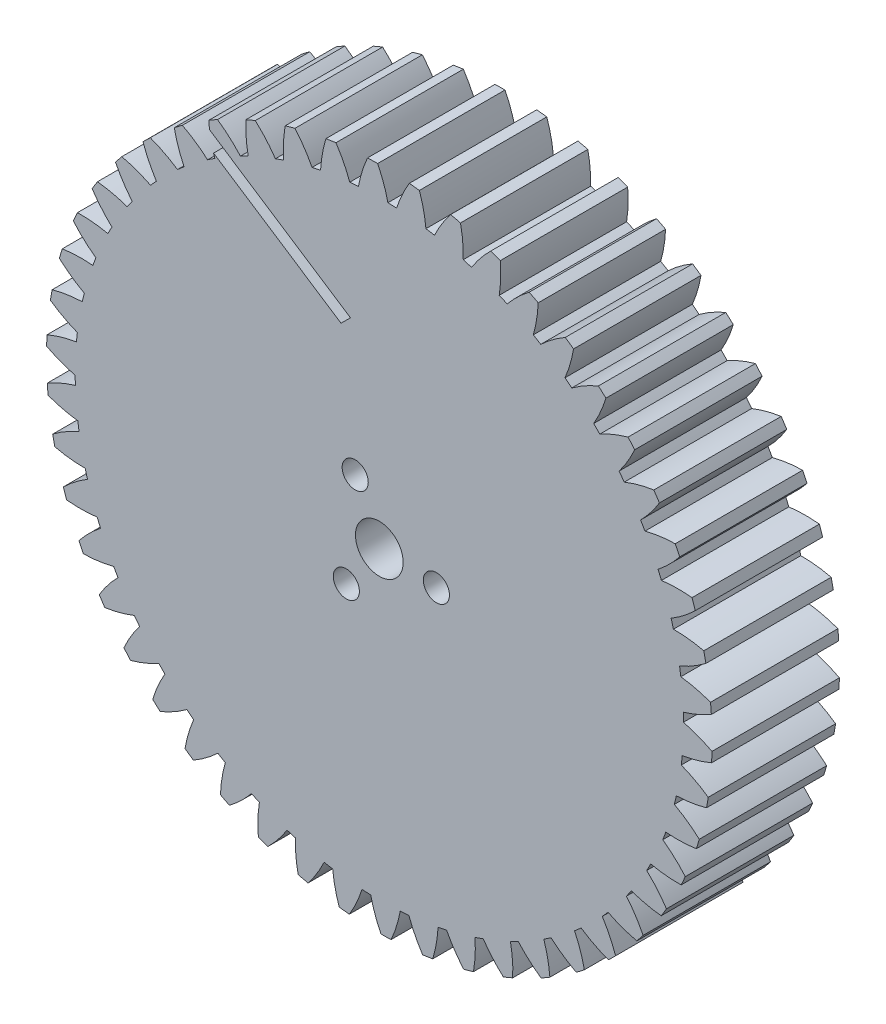
SolidWorks part; units mm, degrees
ref_plane "Front Plane" through (0, 0, 0) normal (0, 0, 1) x (1, 0, 0)
ref_plane "Top Plane" through (0, 0, 0) normal (0, 1, 0) x (1, 0, 0)
ref_plane "Right Plane" through (0, 0, 0) normal (1, 0, 0) x (0, 0, -1)
sketch "Sketch1" plane through (0, 0, 0) normal (0, 0, 1) x (1, 0, 0)
  circle A0 centre (0, 0) radius 52.3715
extrude "Boss-Extrude1" add sketch "Sketch1" along normal blind 10
extrude "Cut-Extrude1" cut sketch "Sketch2" against normal through all
sketch "Sketch2" plane through (-27.9652, -165.9867, 67.9694) normal (0, 0, 1) x (1, 0, 0)
  circle A200 centre (27.9652, 165.9867) radius 130.5991
  arc A600 (44.796, 182.9215) -> (45.7553, 185.1213) centre (36.0583, 188.041) ccw
  arc A601 (45.7553, 185.1213) -> (45.1635, 185.6549) centre (27.9652, 165.9867) ccw
  arc A602 (45.1635, 185.6549) -> (43.0744, 184.4739) centre (49.0675, 176.3106) ccw
  arc A603 (43.0744, 184.4739) -> (42.5408, 184.8975) centre (27.9652, 165.9867) ccw
  arc A604 (42.5408, 184.8975) -> (43.2168, 187.2001) centre (33.2304, 188.8814) ccw
  arc A605 (43.2168, 187.2001) -> (42.5628, 187.6553) centre (27.9652, 165.9867) ccw
  arc A606 (42.5628, 187.6553) -> (40.6382, 186.2218) centre (47.6071, 178.874) ccw
  arc A607 (40.6382, 186.2218) -> (40.0557, 186.5751) centre (27.9652, 165.9867) ccw
  arc A608 (40.0557, 186.5751) -> (40.4378, 188.9444) centre (30.3194, 189.3608) ccw
  arc A609 (40.4378, 188.9444) -> (39.7319, 189.314) centre (27.9652, 165.9867) ccw
  arc A610 (39.7319, 189.314) -> (38.0021, 187.6506) centre (45.8371, 181.2342) ccw
  arc A611 (38.0021, 187.6506) -> (37.38, 187.9281) centre (27.9652, 165.9867) ccw
  arc A612 (37.38, 187.9281) -> (37.4621, 190.3266) centre (27.3713, 189.4715) ccw
  arc A613 (37.4621, 190.3266) -> (36.7155, 190.6049) centre (27.9652, 165.9867) ccw
  arc A614 (36.7155, 190.6049) -> (35.2078, 188.7377) centre (43.7851, 183.3539) ccw
  arc A615 (35.2078, 188.7377) -> (34.5557, 188.9351) centre (27.9652, 165.9867) ccw
  arc A616 (34.5557, 188.9351) -> (34.3366, 191.3249) centre (24.4325, 189.2119) ccw
  arc A617 (34.3366, 191.3249) -> (33.561, 191.5074) centre (27.9652, 165.9867) ccw
  arc A618 (33.561, 191.5074) -> (32.2992, 189.4661) centre (41.4837, 185.1997) ccw
  arc A619 (32.2992, 189.4661) -> (31.6276, 189.5802) centre (27.9652, 165.9867) ccw
  arc A620 (31.6276, 189.5802) -> (31.1107, 191.9237) centre (21.5495, 188.586) ccw
  arc A621 (31.1107, 191.9237) -> (30.3183, 192.0075) centre (27.9652, 165.9867) ccw
  arc A622 (30.3183, 192.0075) -> (29.3223, 189.8241) centre (38.9691, 186.7425) ccw
  arc A623 (29.3223, 189.8241) -> (28.6416, 189.8531) centre (27.9652, 165.9867) ccw
  arc A624 (28.6416, 189.8531) -> (27.8351, 192.1134) centre (18.7676, 187.6037) ccw
  arc A625 (27.8351, 192.1134) -> (27.0384, 192.0973) centre (27.9652, 165.9867) ccw
  arc A626 (27.0384, 192.0973) -> (26.324, 189.8062) centre (36.2809, 187.958) ccw
  arc A627 (26.324, 189.8062) -> (25.6451, 189.7497) centre (27.9652, 165.9867) ccw
  arc A628 (25.6451, 189.7497) -> (24.5616, 191.8911) centre (16.1308, 186.2805) ccw
  arc A629 (24.5616, 191.8911) -> (23.7732, 191.7752) centre (27.9652, 165.9867) ccw
  arc A630 (23.7732, 191.7752) -> (23.3515, 189.4127) centre (33.4616, 188.827) ccw
  arc A631 (23.3515, 189.4127) -> (22.6851, 189.2715) centre (27.9652, 165.9867) ccw
  arc A632 (22.6851, 189.2715) -> (21.3417, 191.2602) centre (13.6807, 184.6372) ccw
  arc A633 (21.3417, 191.2602) -> (20.5741, 191.0465) centre (27.9652, 165.9867) ccw
  arc A634 (20.5741, 191.0465) -> (20.4519, 188.6497) centre (30.5556, 189.3358) ccw
  arc A635 (20.4519, 188.6497) -> (19.8083, 188.4262) centre (27.9652, 165.9867) ccw
  arc A636 (19.8083, 188.4262) -> (18.2264, 190.2308) centre (11.4558, 182.6998) ccw
  arc A637 (18.2264, 190.2308) -> (17.4916, 189.9225) centre (27.9652, 165.9867) ccw
  arc A638 (17.4916, 189.9225) -> (17.6707, 187.5294) centre (27.6088, 189.4763) ccw
  arc A639 (17.6707, 187.5294) -> (17.0602, 187.2269) centre (27.9652, 165.9867) ccw
  arc A640 (17.0602, 187.2269) -> (15.2646, 188.819) centre (9.4913, 180.4988) ccw
  arc A641 (15.2646, 188.819) -> (14.5742, 188.4211) centre (27.9652, 165.9867) ccw
  arc A642 (14.5742, 188.4211) -> (15.0518, 186.0692) centre (24.6675, 189.2464) ccw
  arc A643 (15.0518, 186.0692) -> (14.4841, 185.6926) centre (27.9652, 165.9867) ccw
  arc A644 (14.4841, 185.6926) -> (12.5031, 187.0472) centre (7.8181, 178.069) ccw
  arc A645 (12.5031, 187.0472) -> (11.868, 186.5659) centre (27.9652, 165.9867) ccw
  arc A646 (11.868, 186.5659) -> (12.6367, 184.2924) centre (21.7783, 188.6497) ccw
  arc A647 (12.6367, 184.2924) -> (12.1206, 183.8476) centre (27.9652, 165.9867) ccw
  arc A648 (12.1206, 183.8476) -> (9.9854, 184.9432) centre (6.4626, 175.4486) ccw
  arc A649 (9.9854, 184.9432) -> (9.4157, 184.3861) centre (27.9652, 165.9867) ccw
  arc A650 (9.4157, 184.3861) -> (10.4632, 182.2269) centre (18.9867, 187.6956) ccw
  arc A651 (10.4632, 182.2269) -> (10.007, 181.7209) centre (27.9652, 165.9867) ccw
  arc A652 (10.007, 181.7209) -> (7.7513, 182.5402) centre (5.4463, 172.679) ccw
  arc A653 (7.7513, 182.5402) -> (7.2559, 181.9161) centre (27.9652, 165.9867) ccw
  arc A654 (7.2559, 181.9161) -> (8.5658, 179.9053) centre (16.3366, 186.3991) ccw
  arc A655 (8.5658, 179.9053) -> (8.1766, 179.3461) centre (27.9652, 165.9867) ccw
  arc A656 (8.1766, 179.3461) -> (5.836, 179.8762) centre (4.7851, 169.8039) ccw
  arc A657 (5.836, 179.8762) -> (5.4228, 179.195) centre (27.9652, 165.9867) ccw
  arc A658 (5.4228, 179.195) -> (6.9743, 177.3641) centre (13.87, 184.7807) ccw
  arc A659 (6.9743, 177.3641) -> (6.6582, 176.7606) centre (27.9652, 165.9867) ccw
  arc A660 (6.6582, 176.7606) -> (4.2697, 176.9932) centre (4.4895, 166.8686) ccw
  arc A661 (4.2697, 176.9932) -> (3.9451, 176.2655) centre (27.9652, 165.9867) ccw
  arc A662 (3.9451, 176.2655) -> (5.7139, 174.6435) centre (11.6256, 182.8659) ccw
  arc A663 (5.7139, 174.6435) -> (5.4759, 174.0052) centre (27.9652, 165.9867) ccw
  arc A664 (5.4759, 174.0052) -> (3.0771, 173.9365) centre (4.564, 163.9193) ccw
  arc A665 (3.0771, 173.9365) -> (2.8462, 173.1739) centre (27.9652, 165.9867) ccw
  arc A666 (2.8462, 173.1739) -> (4.8043, 171.7864) centre (9.6389, 180.6849) ccw
  arc A667 (4.8043, 171.7864) -> (4.6483, 171.1233) centre (27.9652, 165.9867) ccw
  arc A668 (4.6483, 171.1233) -> (2.2769, 170.7545) centre (5.0077, 161.0027) ccw
  arc A669 (2.2769, 170.7545) -> (2.1435, 169.969) centre (27.9652, 165.9867) ccw
  arc A670 (2.1435, 169.969) -> (4.2601, 168.8379) centre (7.9413, 178.2721) ccw
  arc A671 (4.2601, 168.8379) -> (4.1884, 168.1604) centre (27.9652, 165.9867) ccw
  arc A672 (4.1884, 168.1604) -> (1.8819, 167.4974) centre (5.8134, 158.1646) ccw
  arc A673 (1.8819, 167.4974) -> (1.848, 166.7013) centre (27.9652, 165.9867) ccw
  arc A674 (1.848, 166.7013) -> (4.0896, 165.8444) centre (6.5594, 175.6656) ccw
  arc A675 (4.0896, 165.8444) -> (4.1034, 165.1632) centre (27.9652, 165.9867) ccw
  arc A676 (4.1034, 165.1632) -> (1.8983, 164.2163) centre (6.9684, 155.4499) ccw
  arc A677 (1.8983, 164.2163) -> (1.9644, 163.4223) centre (27.9652, 165.9867) ccw
  arc A678 (1.9644, 163.4223) -> (4.2957, 162.8531) centre (5.5151, 172.9064) ccw
  arc A679 (4.2957, 162.8531) -> (4.3948, 162.179) centre (27.9652, 165.9867) ccw
  arc A680 (4.3948, 162.179) -> (2.3257, 160.9632) centre (8.4546, 152.9014) ccw
  arc A681 (2.3257, 160.9632) -> (2.4908, 160.1837) centre (27.9652, 165.9867) ccw
  arc A682 (2.4908, 160.1837) -> (4.8751, 159.9112) centre (4.8249, 170.0381) ccw
  arc A683 (4.8751, 159.9112) -> (5.0579, 159.2549) centre (27.9652, 165.9867) ccw
  arc A684 (5.0579, 159.2549) -> (3.1575, 157.7894) centre (10.2485, 150.5593) ccw
  arc A685 (3.1575, 157.7894) -> (3.419, 157.0367) centre (27.9652, 165.9867) ccw
  arc A686 (3.419, 157.0367) -> (5.8187, 157.0652) centre (4.4996, 167.1059) ccw
  arc A687 (5.8187, 157.0652) -> (6.0822, 156.4369) centre (27.9652, 165.9867) ccw
  arc A688 (6.0822, 156.4369) -> (4.3805, 154.7448) centre (12.3217, 148.4604) ccw
  arc A689 (4.3805, 154.7448) -> (4.7343, 154.0308) centre (27.9652, 165.9867) ccw
  arc A690 (4.7343, 154.0308) -> (7.1115, 154.3598) centre (4.5443, 164.156) ccw
  arc A691 (7.1115, 154.3598) -> (7.4517, 153.7696) centre (27.9652, 165.9867) ccw
  arc A692 (7.4517, 153.7696) -> (5.9755, 151.8775) centre (14.6417, 146.638) ccw
  arc A693 (5.9755, 151.8775) -> (6.4159, 151.2135) centre (27.9652, 165.9867) ccw
  arc A694 (6.4159, 151.2135) -> (8.7331, 151.8378) centre (4.9585, 161.2351) ccw
  arc A695 (8.7331, 151.8378) -> (9.1446, 151.2949) centre (27.9652, 165.9867) ccw
  arc A696 (9.1446, 151.2949) -> (7.9172, 149.2327) centre (17.1718, 145.1207) ccw
  arc A697 (7.9172, 149.2327) -> (8.4374, 148.6291) centre (27.9652, 165.9867) ccw
  arc A698 (8.4374, 148.6291) -> (10.6581, 149.539) centre (5.7354, 158.389) ccw
  arc A699 (10.6581, 149.539) -> (11.1344, 149.0519) centre (27.9652, 165.9867) ccw
  arc A700 (11.1344, 149.0519) -> (10.1751, 146.8521) centre (19.8721, 143.9324) ccw
  arc A701 (10.1751, 146.8521) -> (10.7669, 146.3185) centre (27.9652, 165.9867) ccw
  arc A702 (10.7669, 146.3185) -> (12.856, 147.4995) centre (6.8629, 155.6628) ccw
  arc A703 (12.856, 147.4995) -> (13.3896, 147.076) centre (27.9652, 165.9867) ccw
  arc A704 (13.3896, 147.076) -> (12.7136, 144.7733) centre (22.7001, 143.092) ccw
  arc A705 (12.7136, 144.7733) -> (13.3676, 144.3181) centre (27.9652, 165.9867) ccw
  arc A706 (13.3676, 144.3181) -> (15.2922, 145.7516) centre (8.3233, 153.0994) ccw
  arc A707 (15.2922, 145.7516) -> (15.8747, 145.3983) centre (27.9652, 165.9867) ccw
  arc A708 (15.8747, 145.3983) -> (15.4926, 143.029) centre (25.6111, 142.6127) ccw
  arc A709 (15.4926, 143.029) -> (16.1985, 142.6594) centre (27.9652, 165.9867) ccw
  arc A710 (16.1985, 142.6594) -> (17.9283, 144.3228) centre (10.0934, 150.7392) ccw
  arc A711 (17.9283, 144.3228) -> (18.5505, 144.0453) centre (27.9652, 165.9867) ccw
  arc A712 (18.5505, 144.0453) -> (18.4683, 141.6468) centre (28.5592, 142.5019) ccw
  arc A713 (18.4683, 141.6468) -> (19.215, 141.3686) centre (27.9652, 165.9867) ccw
  arc A714 (19.215, 141.3686) -> (20.7226, 143.2357) centre (12.1453, 148.6195) ccw
  arc A715 (20.7226, 143.2357) -> (21.3747, 143.0383) centre (27.9652, 165.9867) ccw
  arc A716 (21.3747, 143.0383) -> (21.5938, 140.6485) centre (31.4979, 142.7615) ccw
  arc A717 (21.5938, 140.6485) -> (22.3694, 140.466) centre (27.9652, 165.9867) ccw
  arc A718 (22.3694, 140.466) -> (23.6312, 142.5074) centre (14.4467, 146.7737) ccw
  arc A719 (23.6312, 142.5074) -> (24.3029, 142.3933) centre (27.9652, 165.9867) ccw
  arc A720 (24.3029, 142.3933) -> (24.8198, 140.0497) centre (34.3809, 143.3874) ccw
  arc A721 (24.8198, 140.0497) -> (25.6121, 139.9659) centre (27.9652, 165.9867) ccw
  arc A722 (25.6121, 139.9659) -> (26.6081, 142.1493) centre (16.9614, 145.2309) ccw
  arc A723 (26.6081, 142.1493) -> (27.2888, 142.1203) centre (27.9652, 165.9867) ccw
  arc A724 (27.2888, 142.1203) -> (28.0953, 139.86) centre (37.1628, 144.3697) ccw
  arc A725 (28.0953, 139.86) -> (28.892, 139.8762) centre (27.9652, 165.9867) ccw
  arc A726 (28.892, 139.8762) -> (29.6065, 142.1672) centre (19.6495, 144.0154) ccw
  arc A727 (29.6065, 142.1672) -> (30.2854, 142.2237) centre (27.9652, 165.9867) ccw
  arc A728 (30.2854, 142.2237) -> (31.3689, 140.0824) centre (39.7996, 145.693) ccw
  arc A729 (31.3689, 140.0824) -> (32.1572, 140.1982) centre (27.9652, 165.9867) ccw
  arc A730 (32.1572, 140.1982) -> (32.5789, 142.5607) centre (22.4688, 143.1464) ccw
  arc A731 (32.5789, 142.5607) -> (33.2454, 142.7019) centre (27.9652, 165.9867) ccw
  arc A732 (33.2454, 142.7019) -> (34.5887, 140.7132) centre (42.2498, 147.3362) ccw
  arc A733 (34.5887, 140.7132) -> (35.3563, 140.9269) centre (27.9652, 165.9867) ccw
  arc A734 (35.3563, 140.9269) -> (35.4786, 143.3237) centre (25.3748, 142.6377) ccw
  arc A735 (35.4786, 143.3237) -> (36.1221, 143.5473) centre (27.9652, 165.9867) ccw
  arc A736 (36.1221, 143.5473) -> (37.7041, 141.7426) centre (44.4746, 149.2736) ccw
  arc A737 (37.7041, 141.7426) -> (38.4388, 142.0509) centre (27.9652, 165.9867) ccw
  arc A738 (38.4388, 142.0509) -> (38.2598, 144.4441) centre (28.3217, 142.4971) ccw
  arc A739 (38.2598, 144.4441) -> (38.8702, 144.7465) centre (27.9652, 165.9867) ccw
  arc A740 (38.8702, 144.7465) -> (40.6659, 143.1544) centre (46.4392, 151.4746) ccw
  arc A741 (40.6659, 143.1544) -> (41.3562, 143.5523) centre (27.9652, 165.9867) ccw
  arc A742 (41.3562, 143.5523) -> (40.8786, 145.9042) centre (31.2629, 142.727) ccw
  arc A743 (40.8786, 145.9042) -> (41.4463, 146.2808) centre (27.9652, 165.9867) ccw
  arc A744 (41.4463, 146.2808) -> (43.4274, 144.9263) centre (48.1123, 153.9044) ccw
  arc A745 (43.4274, 144.9263) -> (44.0624, 145.4076) centre (27.9652, 165.9867) ccw
  arc A746 (44.0624, 145.4076) -> (43.2938, 147.681) centre (34.1521, 143.3237) ccw
  arc A747 (43.2938, 147.681) -> (43.8098, 148.1258) centre (27.9652, 165.9867) ccw
  arc A748 (43.8098, 148.1258) -> (45.945, 147.0303) centre (49.4678, 156.5248) ccw
  arc A749 (45.945, 147.0303) -> (46.5147, 147.5874) centre (27.9652, 165.9867) ccw
  arc A750 (46.5147, 147.5874) -> (45.4672, 149.7465) centre (36.9437, 144.2778) ccw
  arc A751 (45.4672, 149.7465) -> (45.9234, 150.2525) centre (27.9652, 165.9867) ccw
  arc A752 (45.9234, 150.2525) -> (48.1791, 149.4332) centre (50.4841, 159.2944) ccw
  arc A753 (48.1791, 149.4332) -> (48.6745, 150.0573) centre (27.9652, 165.9867) ccw
  arc A754 (48.6745, 150.0573) -> (47.3646, 152.0682) centre (39.5938, 145.5743) ccw
  arc A755 (47.3646, 152.0682) -> (47.7538, 152.6273) centre (27.9652, 165.9867) ccw
  arc A756 (47.7538, 152.6273) -> (50.0944, 152.0972) centre (51.1453, 162.1695) ccw
  arc A757 (50.0944, 152.0972) -> (50.5077, 152.7785) centre (27.9652, 165.9867) ccw
  arc A758 (50.5077, 152.7785) -> (48.9561, 154.6093) centre (42.0604, 147.1927) ccw
  arc A759 (48.9561, 154.6093) -> (49.2722, 155.2128) centre (27.9652, 165.9867) ccw
  arc A760 (49.2722, 155.2128) -> (51.6607, 154.9803) centre (51.441, 165.1049) ccw
  arc A761 (51.6607, 154.9803) -> (51.9853, 155.7079) centre (27.9652, 165.9867) ccw
  arc A762 (51.9853, 155.7079) -> (50.2166, 157.3299) centre (44.3048, 149.1075) ccw
  arc A763 (50.2166, 157.3299) -> (50.4545, 157.9683) centre (27.9652, 165.9867) ccw
  arc A764 (50.4545, 157.9683) -> (52.8534, 158.0369) centre (51.3664, 168.0541) ccw
  arc A765 (52.8534, 158.0369) -> (53.0842, 158.7995) centre (27.9652, 165.9867) ccw
  arc A766 (53.0842, 158.7995) -> (51.1261, 160.187) centre (46.2915, 151.2885) ccw
  arc A767 (51.1261, 160.187) -> (51.2821, 160.8501) centre (27.9652, 165.9867) ccw
  arc A768 (51.2821, 160.8501) -> (53.6535, 161.2189) centre (50.9227, 170.9708) ccw
  arc A769 (53.6535, 161.2189) -> (53.7869, 162.0044) centre (27.9652, 165.9867) ccw
  arc A770 (53.7869, 162.0044) -> (51.6704, 163.1356) centre (47.9891, 153.7013) ccw
  arc A771 (51.6704, 163.1356) -> (51.7421, 163.813) centre (27.9652, 165.9867) ccw
  arc A772 (51.7421, 163.813) -> (54.0485, 164.4761) centre (50.117, 173.8088) ccw
  arc A773 (54.0485, 164.4761) -> (54.0824, 165.2722) centre (27.9652, 165.9867) ccw
  arc A774 (54.0824, 165.2722) -> (51.8408, 166.1291) centre (49.371, 156.3079) ccw
  arc A775 (51.8408, 166.1291) -> (51.827, 166.8102) centre (27.9652, 165.9867) ccw
  arc A776 (51.827, 166.8102) -> (54.0322, 167.7571) centre (48.962, 176.5235) ccw
  arc A777 (54.0322, 167.7571) -> (53.9661, 168.5511) centre (27.9652, 165.9867) ccw
  arc A778 (53.9661, 168.5511) -> (51.6347, 169.1204) centre (50.4153, 159.067) ccw
  arc A779 (51.6347, 169.1204) -> (51.5356, 169.7944) centre (27.9652, 165.9867) ccw
  arc A780 (51.5356, 169.7944) -> (53.6047, 171.0102) centre (47.4758, 179.072) ccw
  arc A781 (53.6047, 171.0102) -> (53.4396, 171.7897) centre (27.9652, 165.9867) ccw
  arc A782 (53.4396, 171.7897) -> (51.0553, 172.0622) centre (51.1056, 161.9353) ccw
  arc A783 (51.0553, 172.0622) -> (50.8726, 172.7185) centre (27.9652, 165.9867) ccw
  arc A784 (50.8726, 172.7185) -> (52.7729, 174.1841) centre (45.682, 181.4141) ccw
  arc A785 (52.7729, 174.1841) -> (52.5114, 174.9367) centre (27.9652, 165.9867) ccw
  arc A786 (52.5114, 174.9367) -> (50.1118, 174.9083) centre (51.4309, 164.8675) ccw
  arc A787 (50.1118, 174.9083) -> (49.8482, 175.5365) centre (27.9652, 165.9867) ccw
  arc A788 (49.8482, 175.5365) -> (51.5499, 177.2287) centre (43.6087, 183.513) ccw
  arc A789 (51.5499, 177.2287) -> (51.1962, 177.9426) centre (27.9652, 165.9867) ccw
  arc A790 (51.1962, 177.9426) -> (48.819, 177.6136) centre (51.3861, 167.8174) ccw
  arc A791 (48.819, 177.6136) -> (48.4787, 178.2038) centre (27.9652, 165.9867) ccw
  arc A792 (48.4787, 178.2038) -> (49.955, 180.096) centre (41.2887, 185.3354) ccw
  arc A793 (49.955, 180.096) -> (49.5145, 180.7599) centre (27.9652, 165.9867) ccw
  arc A794 (49.5145, 180.7599) -> (47.1973, 180.1356) centre (50.972, 170.7384) ccw
  arc A795 (47.1973, 180.1356) -> (46.7858, 180.6785) centre (27.9652, 165.9867) ccw
  arc A796 (46.7858, 180.6785) -> (48.0132, 182.7407) centre (38.7586, 186.8527) ccw
  arc A797 (48.0132, 182.7407) -> (47.493, 183.3443) centre (27.9652, 165.9867) ccw
  arc A798 (47.493, 183.3443) -> (45.2723, 182.4344) centre (50.195, 173.5844) ccw
  arc A799 (45.2723, 182.4344) -> (44.796, 182.9215) centre (27.9652, 165.9867) ccw
hole_wizard "Ø2.05 (2.05) Diameter Hole1" positions "Sketch3" profile "Sketch4" hole size "Ø2.05" standard "ISO" end condition through all
sketch "Sketch3" plane through (-27.9652, -165.9867, 75.1531) normal (0, 0, 1) x (1, 0, 0)
  circle A0 centre (27.9652, 165.9867) radius 4.5
  point P0 (32.4472, 165.5842)
  point P2 (25.3756, 162.3065)
  point P4 (26.0728, 170.0695)
sketch "Sketch4" plane through (4.482, -0.4025, 75.1531) normal (1, 0, 0) x (0, -1, 0)
  line L0 (0, 0) -> (0, 75.1531)
  line L1 (0, 75.1531) -> (1.025, 75.1531)
  line L2 (1.025, 75.1531) -> (1.025, 0)
  line L3 (1.025, 0) -> (0, 0)
  line L4 (0, -6.35) -> (0, 107.95) construction
  dimension "Thru Hole Dia." = 2.05
  dimension "Thru Hole Depth" = 75.1531
extrude "Cut-Extrude2" cut sketch "Sketch5" against normal through all
sketch "Sketch5" plane through (-27.9652, -165.9867, 75.1531) normal (0, 0, 1) x (1, 0, 0)
  circle A3 centre (27.9652, 165.9867) radius 1.873
extrude "Cut-Extrude3" cut sketch "Sketch6" against normal through all
sketch "Sketch6" plane through (-27.9652, -165.9867, 67.9694) normal (0, 0, 1) x (1, 0, 0)
  line L0 (24.9619, 179.8217) -> (25.6984, 180.5582)
  line L1 (25.6984, 180.5582) -> (13.0377, 188.8575)
  line L2 (24.9619, 179.8217) -> (12.4787, 188.0048)
  line L3 (12.4787, 188.0048) -> (13.0377, 188.8575)
